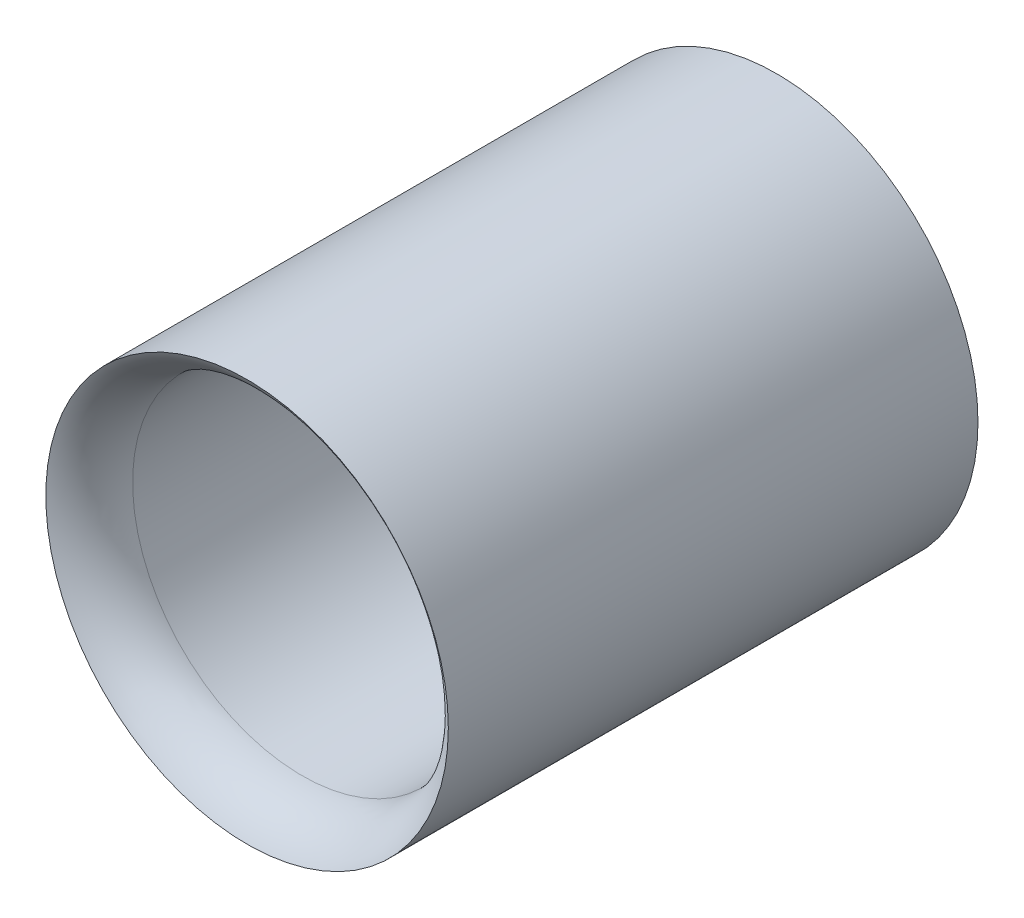
SolidWorks part; units mm, degrees
material "Copper"
ref_plane "Front Plane" through (0, 0, 0) normal (0, 0, 1) x (1, 0, 0)
ref_plane "Top Plane" through (0, 0, 0) normal (0, 1, 0) x (1, 0, 0)
ref_plane "Right Plane" through (0, 0, 0) normal (1, 0, 0) x (0, 0, -1)
sketch "Sketch1" plane through (0, 0, 0) normal (0, 0, 1) x (1, 0, 0)
  circle A0 centre (0, 0) radius 9.5
  circle A2 centre (0, 0) radius 8
  dimension "D1" = 19
  dimension "D2" = 1.5
extrude "Boss-Extrude1" add sketch "Sketch1" along normal blind 25
fillet "Fillet3" radius 3 1 edges at (8, 0, 25)
